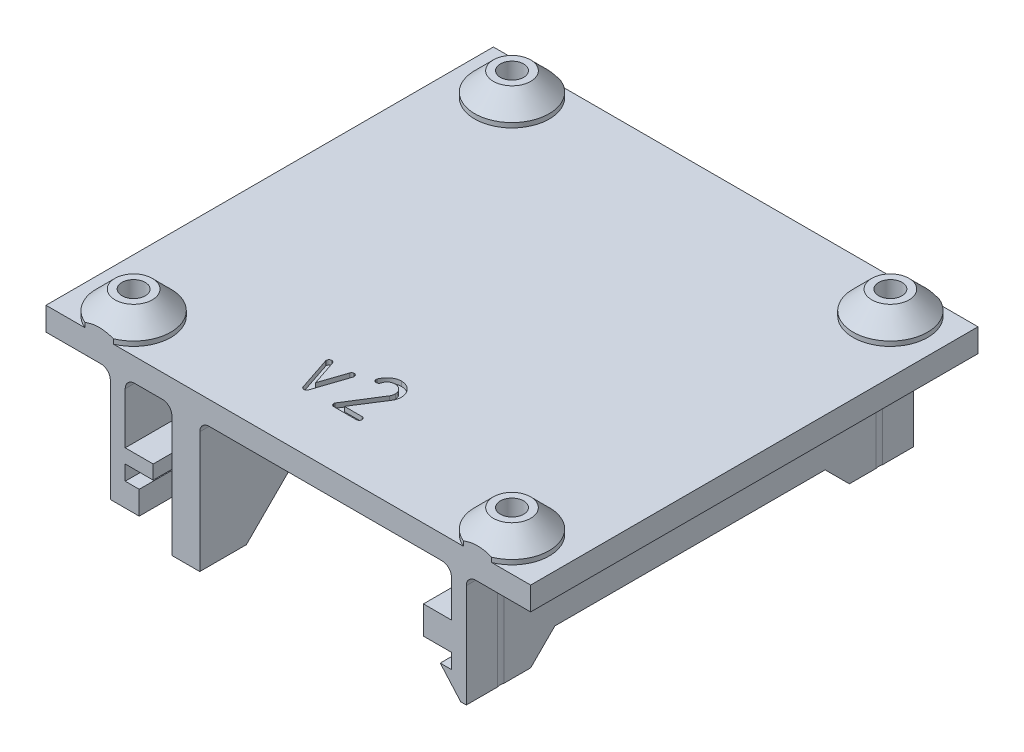
SolidWorks part; units mm, degrees
material "ABS_eSun_GRN"
ref_plane "Front Plane" through (0, 0, 0) normal (0, 0, 1) x (1, 0, 0)
ref_plane "Top Plane" through (0, 0, 0) normal (0, 1, 0) x (1, 0, 0)
ref_plane "Right Plane" through (0, 0, 0) normal (1, 0, 0) x (0, 0, -1)
sketch "Sketch1" plane through (0, 0, 0) normal (0, 0, 1) x (1, 0, 0)
  line L0 (-17.5, 0) -> (17.5, 0) construction
  line L1 (-17.5, 0) -> (-17.5, -1.6)
  line L2 (-17.5, -1.6) -> (-16, -1.6)
  line L3 (-16, -1.6) -> (-16, -4.1)
  line L4 (-16, -4.1) -> (-19.1, -4.1)
  line L5 (-19.1, -4.1) -> (-19.1, 8)
  line L6 (-26, 10.5) -> (26, 10.5)
  line L7 (19.1, 8) -> (19.1, -4.1)
  line L12 (17.5, 8) -> (-9.5, 8)
  line L16 (-14.5, 0) -> (-14.5, 1.5)
  line L17 (-17.5, 8) -> (-12.5, 8)
  line L19 (-14.5, 0) -> (-17.5, 0)
  line L20 (-12.5, 8) -> (-12.5, -6)
  line L21 (-12.5, -6) -> (-9.5, -6)
  line L22 (-9.5, -6) -> (-9.5, 8)
  line L27 (17.5, 0) -> (14.5, 0)
  line L29 (19.1, -4.1) -> (18.5, -4.1)
  line L34 (17.5, -1.6) -> (16.3, -1.6)
  line L35 (16.3, -1.6) -> (18.5, -4.1)
  line L36 (-19.1, 8) -> (-26, 8)
  line L37 (-26, 8) -> (-26, 10.5)
  line L40 (26, 10.5) -> (26, 8)
  line L41 (26, 8) -> (19.1, 8)
  line L42 (-17.5, 1.5) -> (-17.5, 8)
  line L43 (-17.5, 1.5) -> (-14.5, 1.5)
  line L44 (17.5, -1.6) -> (17.5, 0)
  line L45 (-19.1, 8) -> (-17.5, 8) construction
  line L46 (17.5, 8) -> (19.1, 8) construction
  line L47 (17.5, 0) -> (19.1, 0) construction
  line L48 (14.5, 0) -> (14.5, 3)
  line L49 (14.5, 3) -> (17.5, 3)
  line L50 (17.5, 3) -> (17.5, 8)
  point P12 (0, 10.5)
  dimension "D3" = 2.5
  dimension "D5" = 1.6
  dimension "D6" = 1.2
  dimension "D7" = 3
  dimension "D10" = 2.5
  dimension "D12" = 1.6
  dimension "D13" = 1.5
  dimension "D17" = 52
  dimension "D4" = 1
  dimension "D8" = 8
  dimension "D2" = 6
  dimension "D9" = 12.5
  dimension "D14" = 35
  dimension "D11" = 3
  dimension "D15" = 1.5
extrude "mainBoss" add sketch "Sketch1" along normal mid plane 48
sketch "Sketch5" plane through (0, 10.5, 0) normal (0, 1, 0) x (1, 0, 0)
  line L1 (-20.3, -20.3) -> (20.3, -20.3) construction
  line L2 (-20.3, -20.3) -> (-20.3, 20.3) construction
  line L3 (-20.3, 20.3) -> (20.3, 20.3) construction
  line L4 (20.3, -20.3) -> (20.3, 20.3) construction
  line L5 (-20.3, -20.3) -> (20.3, 20.3) construction
  line L6 (-20.3, 20.3) -> (20.3, -20.3) construction
  circle A0 centre (-20.3, 20.3) radius 1.25
  circle A1 centre (20.3, 20.3) radius 1.25
  circle A2 centre (20.3, -20.3) radius 1.25
  circle A3 centre (-20.3, -20.3) radius 1.25
  point P0 (0, 0)
  dimension "D1" = 2.5
  dimension "D2" = 40.6
sketch "Sketch6" plane through (0, 10.5, 0) normal (0, 1, 0) x (1, 0, 0)
  circle A0 centre (-20.3, 20.3) radius 4
  circle A1 centre (20.3, 20.3) radius 4
  circle A2 centre (20.3, -20.3) radius 4
  circle A3 centre (-20.3, -20.3) radius 4
  dimension "D1" = 8
extrude "mounds" add sketch "Sketch6" along normal blind 2.5
extrude "cut_4holes" cut sketch "Sketch5" against normal through all both and the other way through all contours A1
chamfer "chamf_mounds" distance 2 angle 45 4 edges at (20.3, 13, 24.3) (20.3, 13, -16.3) (-20.3, 13, -16.3) (-20.3, 13, 24.3)
sketch "Sketch7" plane through (0, 0, 0) normal (1, 0, 0) x (0, 0, -1)
  line L0 (-19, -6) -> (-14.5, -1.5)
  line L1 (-14.5, 1.5) -> (-14.5, -1.5) construction
  line L2 (-14.5, -1.5) -> (14.5, -1.5)
  line L3 (14.5, -1.5) -> (19, -6)
  line L4 (19, -6) -> (-19, -6)
  line L5 (-24, -6) -> (24, -6) construction
  line L6 (-19, 7) -> (19, 7)
  line L7 (19, 7) -> (19, 6)
  line L8 (19, 6) -> (14.5, 1.5)
  line L9 (14.5, 1.5) -> (-14.5, 1.5)
  line L10 (-14.5, 1.5) -> (-19, 6)
  line L11 (-19, 6) -> (-19, 7)
  line L12 (-24, 8) -> (24, 8) construction
  point P2 (-14.5, 0)
  point P8 (0, -1.5)
  point P9 (0, -6)
  point P16 (0, 7)
  dimension "D1" = 45
  dimension "D2" = 38
  dimension "D3" = 45
  dimension "D5" = 1
  dimension "D6" = 3
  dimension "D7" = 1
extrude "remove material" cut sketch "Sketch7" against normal through all both and the other way through all
sketch "Sketch8" plane through (0, 0, 0) normal (1, 0, 0) x (0, 0, -1)
  line L0 (24, -4.1) -> (24, 8) construction
  line L1 (-24, 13.9133) -> (24, 13.9133)
  line L2 (-24, 13.9133) -> (-24, -11.0488)
  line L3 (-24, -11.0488) -> (24, -11.0488)
  line L4 (24, 13.9133) -> (24, -11.0488)
  line L5 (-24, -4.1) -> (-24, 8) construction
extrude "Cut-Extrude1" cut sketch "Sketch8" against normal through all both and the other way through all flip side to cut
fillet "Fillet2" radius 1 6 edges at (-12.5, 8, 0) (-9.5, 8, 0) (19.1, 8, 22.325) (-19.1, 8, 22.325) (-17.5, 8, 0) (17.5, 8, 0)
sketch "version" plane through (0, 10.5, 0) normal (0, 1, 0) x (1, 0, 0)
  line L0 (-6.4482, -18) -> (6.4482, -18) construction
  line L1 (18.7801, -24) -> (-18.7801, -24) construction
  text T0 "v2" font "DS ISO 1" height 6
  point P3 (0, -18)
  dimension "D1" = 6
extrude "VersionNo" cut sketch "version" against normal blind 0.5
equation "\"width\"=48"
equation "\"D1@mainBoss\" = \"width\""
equation "\"diam_holes\"=2.5"
equation "\"hole_dist1\"=43"
equation "\"arm_length\"=8"
equation "\"D8@Sketch1\"=\"arm_length\""
equation "\"diam_hole\"=2.5"
equation "\"D1@Sketch5\"=\"diam_hole\""
